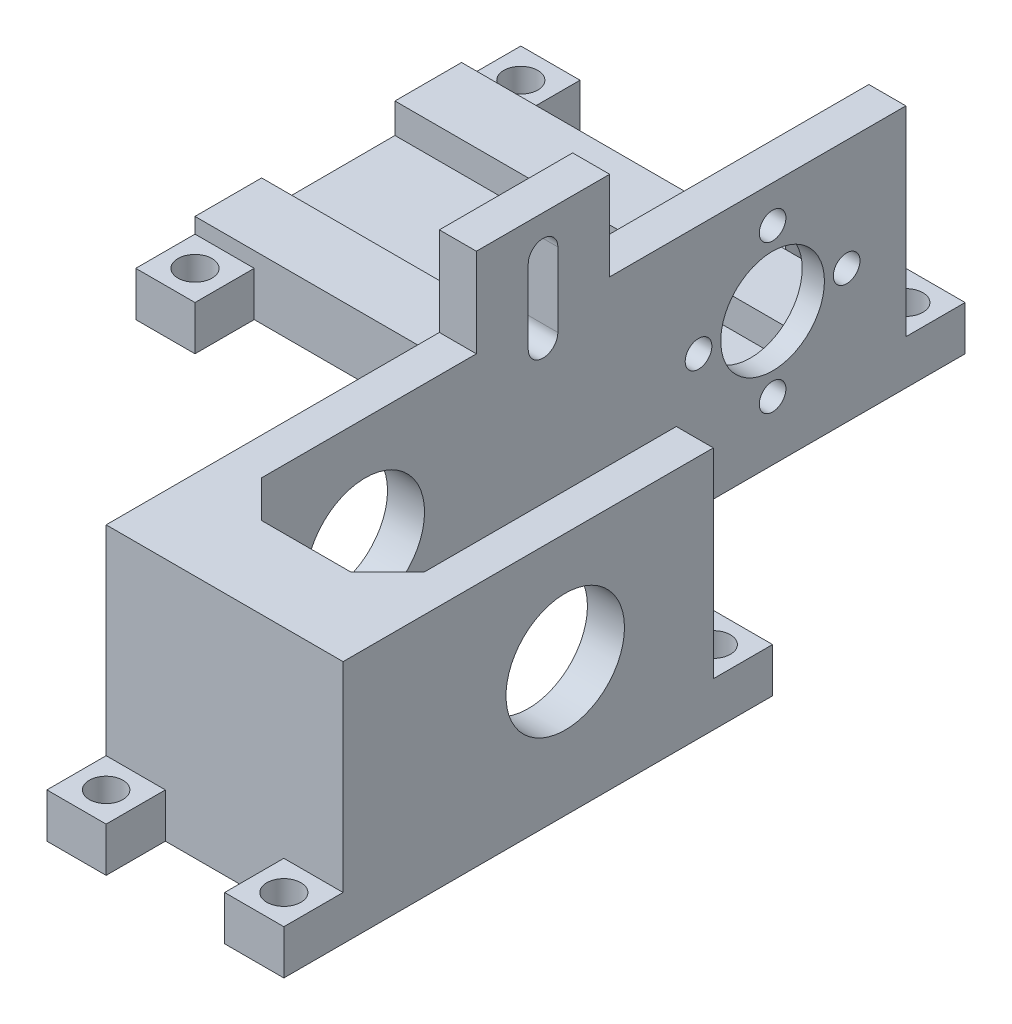
SolidWorks part; units mm, degrees
ref_plane "Plan de face" through (0, 0, 0) normal (0, 0, 1) x (1, 0, 0)
ref_plane "Plan de dessus" through (0, 0, 0) normal (0, 1, 0) x (1, 0, 0)
ref_plane "Plan de droite" through (0, 0, 0) normal (1, 0, 0) x (0, 0, -1)
sketch "Esquisse1" plane through (0, 0, 0) normal (0, 1, 0) x (1, 0, 0)
  line L0 (0, 0) -> (17, 0)
  line L1 (0, 0) -> (-15, 0)
  line L2 (-15, 0) -> (-15, 50)
  line L3 (-15, 50) -> (-10, 50)
  line L4 (-10, 50) -> (-10, 6)
  line L5 (17, 0) -> (17, 50)
  line L6 (17, 50) -> (12, 50)
  line L7 (12, 50) -> (12, 6)
  line L8 (12, 6) -> (-10, 6)
  line L9 (-15, 0) -> (-15, 103)
  line L10 (-10, 73) -> (-70, 73)
  line L11 (-70, 73) -> (-70, 103)
  line L12 (-70, 103) -> (-10, 103)
  line L17 (-10, 50) -> (-10, 103) construction
  line L18 (-10, 103) -> (-15, 103)
  line L19 (-10, 103) -> (-10, 73)
  line L20 (-10, 73) -> (-10, 50)
extrude "Boss.-Extru.1" add sketch "Esquisse1" along normal blind 45 contours L20 L9 L3 | L9 | L7 L8 L4 L3 L2 L1 L0 L5 L6 region at (-7.5, 0, -0.5936) region at (-12.5, 0, -61.5) region at (-12.5, 0, -88)
sketch "Esquisse2" plane through (17, 0, 0) normal (1, 0, 0) x (0, 0, -1)
  line L0 (0, 0) -> (30, 0) construction
  line L2 (0, 0) -> (103, 0) construction
  line L3 (30, 0) -> (30, 18) construction
  circle A0 centre (30, 18) radius 8
extrude "Enlèv. mat.-Extru.1" cut sketch "Esquisse2" against normal blind 50
sketch "Esquisse3" plane through (-15, 0, 0) normal (-1, 0, 0) x (0, 0, 1)
  line L0 (0, 0) -> (-54, 0) construction
  line L1 (0, 0) -> (-103, 0) construction
  line L3 (0, 45) -> (-103, 45) construction
  line L4 (-54, 45) -> (-54, 40) construction
  line L5 (-52, 40) -> (-52, 30)
  line L6 (-52, 30) -> (-56, 30) construction
  line L7 (-56, 30) -> (-56, 40)
  circle A0 centre (-54, 40) radius 2
  circle A1 centre (-54, 30) radius 2
extrude "Enlèv. mat.-Extru.2" cut sketch "Esquisse3" against normal blind 50 contours A1 L5 A0 L7 | A0 | A1 region at (-15, 40, -54) region at (-15, 35, -54) region at (-15, 30, -54)
sketch "Esquisse4" plane through (-10, 0, 0) normal (1, 0, 0) x (0, 0, -1)
  line L0 (103, 0) -> (67, 0)
  line L1 (103, 0) -> (6, 0) construction
  line L2 (85, 18) -> (85, 8) construction
  line L3 (85, 18) -> (85, 28) construction
  line L4 (85, 28) -> (85, 18) construction
  line L5 (85, 18) -> (75, 18) construction
  line L6 (67, 0) -> (76, 0) construction
  line L7 (85, 18) -> (95, 18) construction
  line L8 (103, 0) -> (94, 0) construction
  line L9 (94, 0) -> (94, 8.0723)
  line L10 (94, 8.0723) -> (103, 8.0723)
  line L11 (103, 45) -> (103, 0) construction
  line L12 (94, 0) -> (85, 0) construction
  line L13 (76, 8.0723) -> (76, 0)
  line L14 (76, 8.0723) -> (67, 8.0723)
  line L15 (67, 8.0723) -> (67, 0)
  line L16 (103, 8.0723) -> (103, 0)
  line L17 (103, 8.0723) -> (103, 0)
  line L18 (94, 0) -> (103, 0)
  line L19 (76, 0) -> (76, 4)
  line L20 (76, 4) -> (94, 4.0361)
  line L21 (94, 4.0361) -> (94, 0)
  circle A0 centre (85, 18) radius 13.4
  circle A1 centre (75, 18) radius 1.8
  circle A2 centre (85, 8) radius 1.8
  circle A3 centre (95, 18) radius 1.8
  circle A4 centre (85, 28) radius 1.8
  circle A5 centre (85, 18) radius 7
  line M8 (6, 0) -> (103, 0)
  line M9 (103, 0) -> (103, 45)
extrude "Enlèv. mat.-Extru.3" cut sketch "Esquisse4" against normal blind 5 contours A2 | A3 | A1 | A4 | A5 region at (-10, 18, -75) region at (-10, 8, -85) region at (-10, 18, -95)
extrude "Boss.-Extru.2" add sketch "Esquisse4<4>" against normal blind 60 contours L10 L9 L0 M9 | L14 L15 L13 M8 | L20 L13 L0 L9 region at (-10, 4.0361, -98.5) region at (-10, 2.009, -85.0135) region at (-10, 4.0361, -71.5)
sketch "Esquisse4<4>" plane through (-10, 0, 0) normal (1, 0, 0) x (0, 0, -1) same geometry as "Esquisse4"
sketch "Esquisse6" plane through (0, 0, 0) normal (0, -1, 0) x (1, 0, 0)
  line L0 (-10, -6) -> (12, -6)
  line L1 (12, -6) -> (12, -16)
  line L2 (12, -50) -> (12, -6) construction
  line L3 (-10, -6) -> (-10, -16)
  line L4 (-10, -103) -> (-10, -6) construction
  line L5 (-10, -6) -> (-5, -6)
  line L6 (-5, -6) -> (-5, -11) construction
  line L7 (12, -6) -> (7, -6)
  line L8 (7, -6) -> (7, -11) construction
  line L9 (7, -11) -> (-5, -11)
  line L10 (-10, -16) -> (-5, -11)
  line L11 (7, -11) -> (12, -16)
  line M9 (-10, -103) -> (-10, -6)
  line M10 (-10, -6) -> (12, -6)
  line M11 (12, -6) -> (12, -50)
extrude "Boss.-Extru.3" add sketch "Esquisse6" against normal blind 45 contours L9 L11 L0 L10 M11 M10 M9 region at (1, 0, -9.2716)
sketch "Esquisse11" plane through (0, 0, 0) normal (0, -1, 0) x (1, 0, 0)
  line L0 (17, 0) -> (17, 8)
  line L1 (17, 8) -> (9, 8)
  line L2 (9, 8) -> (9, 0)
  line L3 (17, 0) -> (-15, 0) construction
  line L4 (9, 0) -> (17, 0)
  line L5 (-15, 0) -> (-15, 8)
  line L6 (-15, 8) -> (-7, 8)
  line L7 (-7, 8) -> (-7, 0)
  line L8 (-7, 0) -> (-15, 0)
  line L9 (-70, -67) -> (-70, -59)
  line L10 (-70, -59) -> (-62, -59)
  line L11 (-62, -59) -> (-62, -67)
  line L12 (-70, -67) -> (-15, -67) construction
  line L13 (-10, -103) -> (-10, -111)
  line L14 (-10, -111) -> (-18, -111)
  line L15 (-18, -111) -> (-18, -103)
  line L16 (-70, -103) -> (-10, -103) construction
  line L17 (-70, -103) -> (-70, -111)
  line L18 (-70, -111) -> (-62, -111)
  line L19 (-62, -111) -> (-62, -103)
  line L20 (-62, -103) -> (-70, -103)
  line L21 (-18, -103) -> (-10, -103)
  line L22 (-62, -67) -> (-70, -67)
  line L23 (-70, -59) -> (-62, -67) construction
  line L24 (-62, -59) -> (-70, -67) construction
  line L25 (-70, -103) -> (-62, -111) construction
  line L26 (-62, -103) -> (-70, -111) construction
  line L27 (-18, -111) -> (-10, -103) construction
  line L28 (-18, -103) -> (-10, -111) construction
  line L29 (-15, 8) -> (-7, 0) construction
  line L30 (-15, 0) -> (-7, 8) construction
  line L31 (9, 8) -> (17, 0) construction
  line L32 (17, 8) -> (9, 0) construction
  line L37 (-23, -103) -> (-23, -111)
  line L45 (-23, -111) -> (-31, -111)
  line L47 (17, -50) -> (17, -58)
  line L48 (17, -58) -> (9, -58)
  line L49 (9, -58) -> (9, -46)
  line L50 (9, -46) -> (12, -46)
  line L51 (12, -50) -> (12, -16) construction
  line L52 (12, -46) -> (12, -50) construction
  line L53 (17, -50) -> (12, -50) construction
  line L54 (12, -50) -> (9, -50) construction
  line L55 (17, -58) -> (9, -50) construction
  line L56 (9, -50) -> (9, -58) construction
  line L57 (17, -50) -> (9, -58) construction
  line L58 (-15, -67) -> (-15, -103) construction
  line L59 (-15, -103) -> (-23, -103)
  line L60 (-31, -111) -> (-31, -103)
  line L61 (-31, -103) -> (-23, -103)
  line L62 (-31, -103) -> (-23, -111) construction
  line L63 (-23, -103) -> (-31, -111) construction
  circle A2 centre (-11, 4) radius 2.268
  circle A3 centre (13, 4) radius 2.3
  circle A4 centre (-66, -63) radius 2.3
  circle A5 centre (-66, -107) radius 2.3
  circle A6 centre (-14, -107) radius 2.3
  circle A8 centre (13, -54) radius 2.3
  circle A9 centre (-27, -107) radius 2.3
  line M9 (-15, -67) -> (-70, -67)
  line M11 (-70, -103) -> (-10, -103)
  line M16 (12, -16) -> (12, -50)
  line M17 (12, -50) -> (17, -50)
  line M18 (17, -50) -> (17, 0)
  line M19 (17, 0) -> (-15, 0)
extrude "Boss.-Extru.6" add sketch "Esquisse11" against normal blind 6 contours L11 L10 L9 A4 M9 | L18 L19 L17 A5 M11 | L7 L6 L5 A2 M19 | L1 L2 L0 A3 M19 | L48 M17 M16 | L48 L49 L47 M18 | L14 L15 L21 L13 | A6 | L37 L45 L60 L61 | A9 region at (13, 0, 0.1131) region at (-11, 0, 0.1131) region at (16.8558, 0, -54) region at (-69.8869, 0, -63) region at (-62.1131, 0, -107)
sketch "Esquisse12" plane through (-15, 0, 0) normal (-1, 0, 0) x (0, 0, 1)
  line L0 (0, 45) -> (0, 33)
  line L1 (0, 45) -> (0, 6) construction
  line L2 (0, 33) -> (-45, 33)
  line L3 (-45, 33) -> (-45, 45)
  line L4 (0, 45) -> (-103, 45) construction
  line L8 (-103, 45) -> (-103, 8.0723) construction
  line L9 (-103, 33) -> (-103, 45)
  line L10 (-103, 45) -> (0, 45)
  line L11 (-45, 45) -> (-63, 45)
  line L12 (-63, 45) -> (-63, 33)
  line L13 (-103, 33) -> (-63, 33)
  line M9 (0, 6) -> (0, 45)
  line M10 (0, 45) -> (-103, 45)
  line M11 (-103, 45) -> (-103, 8.0723)
extrude "Enlèv. mat.-Extru.5" cut sketch "Esquisse12" against normal blind 50 contours L13 L12 L10 M11 | L3 L2 M9 M10 region at (-15, 39, -83) region at (-15, 39, -22.5)
sketch "Esquisse13" plane through (17, 0, 0) normal (1, 0, 0) x (0, 0, -1)
  line L0 (45, 33) -> (50, 33)
  line L1 (50, 45) -> (50, 6) construction
  line L2 (50, 33) -> (50, 45)
  line L3 (50, 45) -> (45, 45)
  line L4 (45, 45) -> (45, 33)
extrude "Enlèv. mat.-Extru.6" cut sketch "Esquisse13" against normal blind 20
sketch "Esquisse24" plane through (-10, 0, 0) normal (1, 0, 0) x (0, 0, -1)
  circle A0 centre (85, 18) radius 13.4
sketch "Esquisse25" plane through (-15, 0, 0) normal (-1, 0, 0) x (0, 0, 1)
  circle A0 centre (-85, 18) radius 13.4
extrude "Enlèv. mat.-Extru.8" cut sketch "Esquisse25" against normal blind 2
